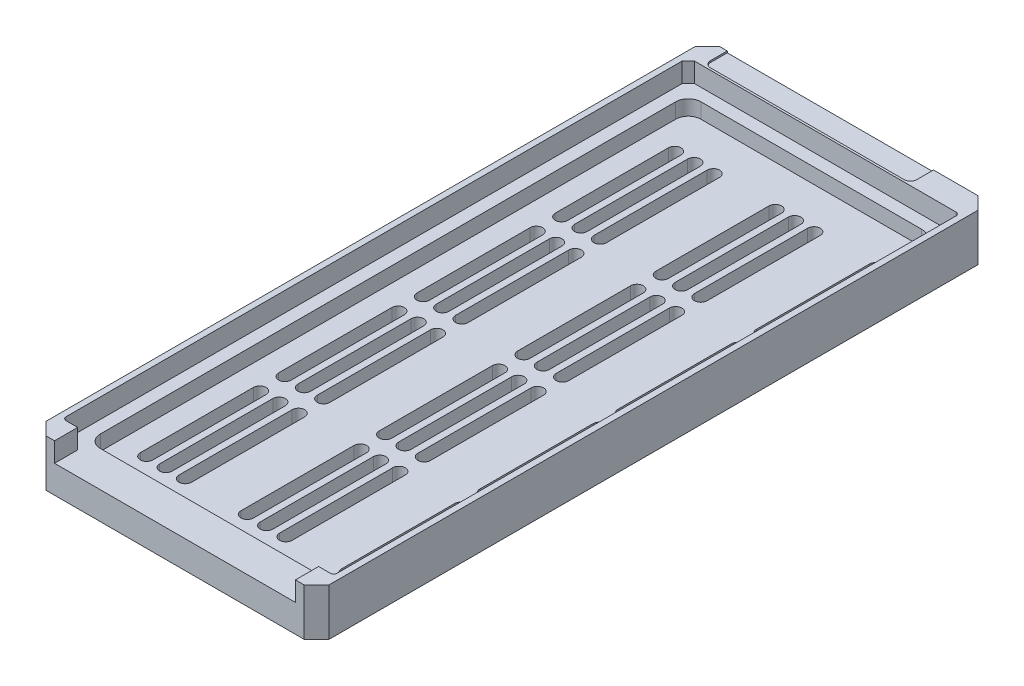
SolidWorks part; units mm, degrees
ref_plane "Front Plane" through (0, 0, 0) normal (0, 0, 1) x (1, 0, 0)
ref_plane "Top Plane" through (0, 0, 0) normal (0, 1, 0) x (1, 0, 0)
ref_plane "Right Plane" through (0, 0, 0) normal (1, 0, 0) x (0, 0, -1)
sketch "Layout" plane through (0, 0, 0) normal (0, 1, 0) x (1, 0, 0)
  line L0 (199.2706, -477.347) -> (192.9206, -477.347) construction
  line L1 (56.0146, -236.0904) -> (192.9206, -236.0904)
  line L2 (56.0146, -236.0904) -> (56.0146, -551.0504)
  line L3 (56.0146, -551.0504) -> (192.9206, -551.0504)
  line L4 (192.9206, -236.0904) -> (192.9206, -551.0504)
  line L5 (199.2706, -162.387) -> (336.1766, -162.387)
  line L6 (199.2706, -162.387) -> (199.2706, -477.347)
  line L7 (199.2706, -477.347) -> (336.1766, -477.347)
  line L8 (336.1766, -162.387) -> (336.1766, -477.347)
  line L9 (342.5266, -18.2355) -> (479.4326, -18.2355)
  line L10 (342.5266, -18.2355) -> (342.5266, -333.1955)
  line L11 (342.5266, -333.1955) -> (479.4326, -333.1955)
  line L12 (479.4326, -18.2355) -> (479.4326, -333.1955)
  line L13 (342.5266, -333.1955) -> (336.1766, -333.1955) construction
  line L14 (410.9796, -18.2355) -> (410.9796, -43.6355) construction
  line L15 (343.0346, -43.6355) -> (478.9246, -43.6355) construction
  circle A0 centre (0, 0) radius 583.8449
  point P16 (479.4326, -18.2355)
  point P17 (336.1766, -162.387)
  point P23 (0, 0)
  dimension "D1" = 1167.6898
  dimension "D2" = 6.35
  dimension "D3" = 314.96
  dimension "D4" = 136.906
  dimension "D5" = 56.0146
  dimension "D6" = 135.89
  dimension "D7" = 25.4
  dimension "D8" = 0.508
sketch "Bolt Pattern" plane through (0, 0, 0) normal (0, 1, 0) x (1, 0, 0)
  line L0 (25.4, -537.525) -> (25.4, -588.325) construction
  line L1 (25.4, -588.325) -> (76.2, -588.325) construction
  point P0 (25.4, -588.325)
  point P5 (76.2, -588.325)
  point P6 (127, -588.325)
  point P7 (177.8, -588.325)
  point P8 (228.6, -588.325)
  point P9 (279.4, -588.325)
  point P10 (330.2, -588.325)
  point P11 (381, -588.325)
  point P12 (431.8, -588.325)
  point P13 (482.6, -588.325)
  point P14 (76.2, -537.525)
  point P15 (127, -537.525)
  point P16 (177.8, -537.525)
  point P17 (228.6, -537.525)
  point P18 (279.4, -537.525)
  point P19 (330.2, -537.525)
  point P20 (381, -537.525)
  point P21 (431.8, -537.525)
  point P22 (482.6, -537.525)
  point P23 (76.2, -486.725)
  point P24 (127, -486.725)
  point P25 (177.8, -486.725)
  point P26 (228.6, -486.725)
  point P27 (279.4, -486.725)
  point P28 (330.2, -486.725)
  point P29 (381, -486.725)
  point P30 (431.8, -486.725)
  point P31 (482.6, -486.725)
  point P32 (76.2, -435.925)
  point P33 (127, -435.925)
  point P34 (177.8, -435.925)
  point P35 (228.6, -435.925)
  point P36 (279.4, -435.925)
  point P37 (330.2, -435.925)
  point P38 (381, -435.925)
  point P39 (431.8, -435.925)
  point P40 (482.6, -435.925)
  point P41 (76.2, -385.125)
  point P42 (127, -385.125)
  point P43 (177.8, -385.125)
  point P44 (228.6, -385.125)
  point P45 (279.4, -385.125)
  point P46 (330.2, -385.125)
  point P47 (381, -385.125)
  point P48 (431.8, -385.125)
  point P49 (482.6, -385.125)
  point P50 (76.2, -334.325)
  point P51 (127, -334.325)
  point P52 (177.8, -334.325)
  point P53 (228.6, -334.325)
  point P54 (279.4, -334.325)
  point P55 (330.2, -334.325)
  point P56 (381, -334.325)
  point P57 (431.8, -334.325)
  point P58 (482.6, -334.325)
  point P59 (76.2, -283.525)
  point P60 (127, -283.525)
  point P61 (177.8, -283.525)
  point P62 (228.6, -283.525)
  point P63 (279.4, -283.525)
  point P64 (330.2, -283.525)
  point P65 (381, -283.525)
  point P66 (431.8, -283.525)
  point P67 (482.6, -283.525)
  point P68 (76.2, -232.725)
  point P69 (127, -232.725)
  point P70 (177.8, -232.725)
  point P71 (228.6, -232.725)
  point P72 (279.4, -232.725)
  point P73 (330.2, -232.725)
  point P74 (381, -232.725)
  point P75 (431.8, -232.725)
  point P76 (482.6, -232.725)
  point P77 (76.2, -181.925)
  point P78 (127, -181.925)
  point P79 (177.8, -181.925)
  point P80 (228.6, -181.925)
  point P81 (279.4, -181.925)
  point P82 (330.2, -181.925)
  point P83 (381, -181.925)
  point P84 (431.8, -181.925)
  point P85 (482.6, -181.925)
  point P86 (76.2, -131.125)
  point P87 (127, -131.125)
  point P88 (177.8, -131.125)
  point P89 (228.6, -131.125)
  point P90 (279.4, -131.125)
  point P91 (330.2, -131.125)
  point P92 (381, -131.125)
  point P93 (431.8, -131.125)
  point P94 (482.6, -131.125)
  point P95 (76.2, -80.325)
  point P96 (127, -80.325)
  point P97 (177.8, -80.325)
  point P98 (228.6, -80.325)
  point P99 (279.4, -80.325)
  point P100 (330.2, -80.325)
  point P101 (381, -80.325)
  point P102 (431.8, -80.325)
  point P103 (482.6, -80.325)
  point P104 (76.2, -29.525)
  point P105 (127, -29.525)
  point P106 (177.8, -29.525)
  point P107 (228.6, -29.525)
  point P108 (279.4, -29.525)
  point P109 (330.2, -29.525)
  point P110 (381, -29.525)
  point P111 (431.8, -29.525)
  point P112 (482.6, -29.525)
  point P113 (25.4, -537.525)
  point P114 (25.4, -486.725)
  point P115 (25.4, -435.925)
  point P116 (25.4, -385.125)
  point P117 (25.4, -334.325)
  point P118 (25.4, -283.525)
  point P119 (25.4, -232.725)
  point P120 (25.4, -181.925)
  point P121 (25.4, -131.125)
  point P122 (25.4, -80.325)
  point P123 (25.4, -29.525)
  dimension "D1" = 588.325
  dimension "D2" = 25.4
  dimension "D5" = 50.8
  dimension "D3" = 10
  dimension "D4" = 12
sketch "Sketch3" plane through (0, 0, 0) normal (0, 1, 0) x (1, 0, 0)
  line L0 (199.2706, -477.347) -> (192.9206, -477.347) construction
  line L1 (52.9666, -223.3904) -> (195.9686, -223.3904)
  line L2 (52.9666, -223.3904) -> (52.9666, -563.7504)
  line L3 (52.9666, -563.7504) -> (195.9686, -563.7504)
  line L4 (195.9686, -223.3904) -> (195.9686, -563.7504)
  line L5 (56.0146, -393.5704) -> (52.9666, -393.5704) construction
  line L6 (56.0146, -236.0904) -> (56.0146, -551.0504) construction
  line L7 (192.9206, -393.5704) -> (195.9686, -393.5704) construction
  line L8 (192.9206, -236.0904) -> (192.9206, -551.0504) construction
  line L9 (124.4676, -236.0904) -> (124.4676, -223.3904) construction
  line L10 (56.0146, -236.0904) -> (192.9206, -236.0904) construction
  line L11 (124.4676, -551.0504) -> (124.4676, -563.7504) construction
  line L12 (56.0146, -551.0504) -> (192.9206, -551.0504) construction
  line L13 (196.0956, -477.347) -> (196.0956, -393.5704) construction
  dimension "D1" = 12.7
  dimension "D2" = 0.254
extrude "Boss-Extrude1" add sketch "Sketch3" along normal blind 23.8252
sketch "Sketch4" plane through (0, 23.8252, 0) normal (0, 1, 0) x (1, 0, 0)
  line L0 (192.9206, -236.0904) -> (192.9206, -551.0504)
  line L1 (192.9206, -551.0504) -> (56.0146, -551.0504)
  line L2 (56.0146, -551.0504) -> (56.0146, -239.2654)
  line L3 (56.0146, -236.0904) -> (56.0146, -551.0504) construction
  line L4 (56.0146, -239.2654) -> (59.1896, -236.0904)
  line L5 (56.0146, -236.0904) -> (192.9206, -236.0904) construction
  line L6 (59.1896, -236.0904) -> (192.9206, -236.0904)
  line L7 (59.1896, -236.0904) -> (56.0146, -236.0904) construction
  line L8 (56.0146, -236.0904) -> (56.0146, -239.2654) construction
  dimension "D1" = 3.175
extrude "Cut-Extrude1" cut sketch "Sketch4" against normal blind 9.8552
other "Move Face1" flip direction yes face at (124.4676, 18.8976, 551.0504) offset 1.016 parameters "D1"=1.016
sketch "Sketch5" plane through (0, 13.97, 0) normal (0, 1, 0) x (1, 0, 0)
  line L18 (62.3646, -545.7164) -> (186.5706, -545.7164)
  line L19 (186.5706, -545.7164) -> (186.5706, -242.4404)
  line L20 (62.3646, -242.4404) -> (62.3646, -545.7164)
  line L21 (186.5706, -242.4404) -> (62.3646, -242.4404)
  line L22 (62.3646, -545.7164) -> (186.5706, -545.7164)
  line L23 (186.5706, -545.7164) -> (186.5706, -242.4404)
  line L24 (62.3646, -242.4404) -> (62.3646, -545.7164)
  line L25 (186.5706, -242.4404) -> (62.3646, -242.4404)
  dimension "D1" = 6.35
extrude "Cut-Extrude2" cut sketch "Sketch5" against normal blind 7.62
sketch "Sketch9" plane through (0, 23.8252, 0) normal (0, 1, 0) x (1, 0, 0)
  line L0 (66.1746, -235.0236) -> (163.9646, -235.0236)
  line L1 (192.9206, -236.0904) -> (59.1896, -236.0904) construction
  line L2 (167.1396, -231.8486) -> (167.1396, -223.3904)
  line L3 (195.9686, -223.3904) -> (52.9666, -223.3904) construction
  line L4 (167.1396, -223.3904) -> (62.9996, -223.3904)
  line L5 (62.9996, -223.3904) -> (62.9996, -231.8486)
  arc A0 (163.9646, -235.0236) -> (167.1396, -231.8486) centre (163.9646, -231.8486) ccw
  arc A1 (62.9996, -231.8486) -> (66.1746, -235.0236) centre (66.1746, -231.8486) ccw
  dimension "D2" = 3.175
  dimension "D1" = 1.0668
  dimension "D3" = 3.81
  dimension "D4" = 104.14
extrude "Cut-Extrude4" cut sketch "Sketch9" against normal blind 0.8382
fillet "Fillet1" radius 6.35 4 edges at (186.5706, 10.16, 242.4404) (186.5706, 10.16, 545.7164) (62.3646, 10.16, 545.7164) (62.3646, 10.16, 242.4404)
fillet "Fillet2" radius 1.778 3 edges at (56.0146, 18.8976, 552.0664) (192.9206, 18.8976, 552.0664) (192.9206, 18.8976, 236.0904)
sketch "Sketch8" plane through (0, 23.8252, 0) normal (0, 1, 0) x (1, 0, 0)
  line L0 (57.7926, -552.0664) -> (191.1426, -552.0664) construction
  line L1 (63.6346, -552.0664) -> (185.3006, -552.0664)
  line L2 (63.6346, -552.0664) -> (63.6346, -563.7504)
  line L3 (63.6346, -563.7504) -> (185.3006, -563.7504)
  line L4 (185.3006, -552.0664) -> (185.3006, -563.7504)
  line L5 (52.9666, -563.7504) -> (195.9686, -563.7504) construction
  line L6 (63.6346, -557.9084) -> (52.9666, -557.9084) construction
  line L7 (52.9666, -223.3904) -> (52.9666, -563.7504) construction
  line L8 (185.3006, -557.9084) -> (195.9686, -557.9084) construction
  line L9 (195.9686, -563.7504) -> (195.9686, -223.3904) construction
  line L10 (56.0146, -239.2654) -> (56.0146, -550.2884) construction
  dimension "D1" = 7.62
extrude "Cut-Extrude3" cut sketch "Sketch8" against normal up to surface (9.8552 mm away) up to face at (124.6883, 13.97, 394.299)
hole_wizard "1/4 (0.25) Diameter Slot1" positions "Sketch6" profile "Sketch7" size "1/4" standard "ANSI Inch" slot yes end condition through all
sketch "Sketch6" plane through (0, 6.35, 0) normal (0, 1, 0) x (1, 0, 0)
  line L0 (76.2, -533.0164) -> (76.2, -469.5164) construction
  line L1 (56.0146, -239.2654) -> (56.0146, -550.2884) construction
  line L2 (68.7146, -545.7164) -> (180.2206, -545.7164) construction
  point P0 (76.2, -501.2664)
  point P5 (127, -501.2664)
  point P39 (85.9596, -501.2664)
  point P41 (136.7596, -501.2664)
  point P55 (95.7196, -501.2664)
  point P57 (146.5196, -501.2664)
  point P73 (177.8, -501.2664)
  dimension "D1" = 63.5
  dimension "D2" = 29.945
  dimension "D3" = 50.8
  dimension "D4" = 39.705
  dimension "D5" = 50.8
  dimension "D6" = 50.8
  dimension "D7" = 12.7
  dimension "D8" = 50.8
sketch "Sketch7" plane through (76.2, 6.35, 501.2664) normal (1, 0, 0) x (0, 0, 1)
  line L0 (0, 0) -> (0, 6.35)
  line L1 (0, 6.35) -> (3.175, 6.35)
  line L2 (3.175, 6.35) -> (3.175, 0)
  line L5 (3.175, 0) -> (0, 0)
  line L11 (0, -6.35) -> (0, 107.95) construction
  dimension "Thru Hole Dia." = 6.35
  dimension "Thru Hole Depth" = 6.35
pattern_linear "LPattern1" count 4 spacing 69.85 along (0, 0, -1) of "1/4 (0.25) Diameter Slot1"
chamfer "Chamfer1" distance 6.35 angle 45 4 edges at (52.9666, 11.9126, 223.3904) (195.9686, 11.9126, 223.3904) (195.9686, 11.9126, 563.7504) (52.9666, 11.9126, 563.7504)
sketch "Sketch10" plane through (0, 13.97, 0) normal (0, 1, 0) x (1, 0, 0)
  line L0 (56.0146, -394.7769) -> (192.9206, -394.0784) construction
  line L1 (56.0146, -239.2654) -> (56.0146, -550.2884) construction
  line L2 (192.9206, -550.2884) -> (192.9206, -237.8684) construction
  line L3 (125.1661, -236.0904) -> (125.1661, -552.0664) construction
  line L4 (191.1426, -236.0904) -> (59.1896, -236.0904) construction
  line L5 (57.7926, -552.0664) -> (63.6346, -552.0664) construction
  point P10 (0, 0)
  dimension "D1" = 315.976
  dimension "D2" = 136.906
